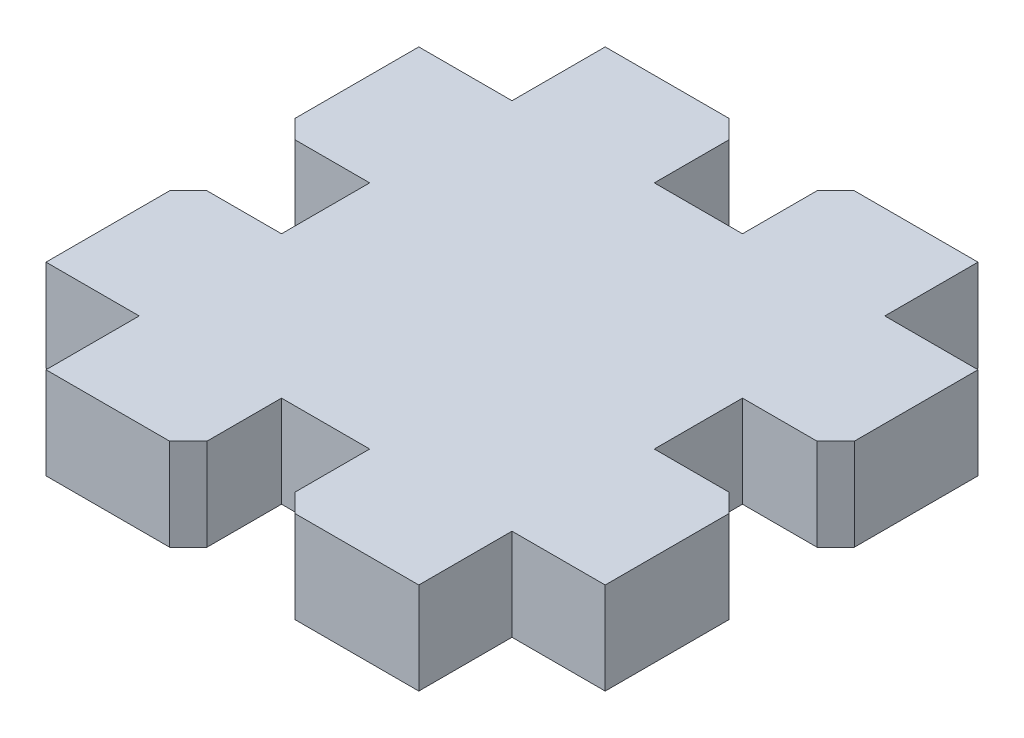
SolidWorks part; units mm, degrees
ref_plane "Front Plane" through (0, 0, 0) normal (0, 0, 1) x (1, 0, 0)
ref_plane "Top Plane" through (0, 0, 0) normal (0, 1, 0) x (1, 0, 0)
ref_plane "Right Plane" through (0, 0, 0) normal (1, 0, 0) x (0, 0, -1)
sketch "Sketch1" plane through (0, 0, 0) normal (0, 1, 0) x (1, 0, 0)
  line L0 (-3.0036, -11.2646) -> (-3.0036, -4.9146)
  line L1 (0, 0) -> (0, 21.9209) construction
  line L2 (-11.8657, 7.7854) -> (8.446, 7.7854) construction
  line L3 (0, 15.5709) -> (0, -6.35) construction
  line L4 (3.0036, 26.8354) -> (3.0036, 20.4854)
  line L5 (-3.0036, 20.4854) -> (3.0036, 20.4854)
  line L7 (-3.0036, 26.8354) -> (-3.0036, 20.4854)
  line L8 (12.7, 4.7819) -> (12.7, 10.789)
  line L9 (12.7, 10.789) -> (19.05, 10.789)
  line L11 (12.7, 4.7819) -> (19.05, 4.7819)
  line L12 (-12.7, 4.7819) -> (-19.05, 4.7819)
  line L14 (-12.7, 10.789) -> (-19.05, 10.789)
  line L16 (-12.7, 4.7819) -> (-12.7, 10.789)
  line L17 (-3.0036, -4.9146) -> (3.0036, -4.9146)
  line L18 (3.0036, -11.2646) -> (3.0036, -4.9146)
  line L19 (-12.7, 26.8354) -> (-3.0036, 26.8354)
  line L20 (-12.7, 26.8354) -> (-12.7, 20.4854)
  line L21 (-12.7, 20.4854) -> (-19.05, 20.4854)
  line L22 (-19.05, 20.4854) -> (-19.05, 10.789)
  line L23 (12.7, 26.8354) -> (3.0036, 26.8354)
  line L24 (12.7, 26.8354) -> (12.7, 20.4854)
  line L25 (12.7, 20.4854) -> (19.05, 20.4854)
  line L26 (19.05, 20.4854) -> (19.05, 10.789)
  line L27 (19.05, -4.9146) -> (19.05, 4.7819)
  line L28 (12.7, -4.9146) -> (19.05, -4.9146)
  line L29 (12.7, -11.2646) -> (12.7, -4.9146)
  line L30 (12.7, -11.2646) -> (3.0036, -11.2646)
  line L31 (-19.05, -4.9146) -> (-19.05, 4.7819)
  line L32 (-12.7, -4.9146) -> (-19.05, -4.9146)
  line L33 (-12.7, -11.2646) -> (-12.7, -4.9146)
  line L34 (-12.7, -11.2646) -> (-3.0036, -11.2646)
  point P3 (0, -4.9146)
  point P13 (0, 20.4854)
  point P22 (12.7, 7.7854)
  dimension "D1" = 12.7
  dimension "D3" = 9.6965
  dimension "2xslotdepth" = 12.7
  dimension "press_fit_slot" = 6.0071
extrude "Boss-Extrude1" add sketch "Sketch1" along normal blind 6.2611
chamfer "Chamfer1" distance 1.27 angle 45 8 edges at (3.0036, 3.1305, -26.8354) (-3.0036, 3.1305, -26.8354) (19.05, 3.1305, -10.789) (19.05, 3.1305, -4.7819) (3.0036, 3.1305, 11.2646) (-3.0036, 3.1305, 11.2646) (-19.05, 3.1305, -4.7819) (-19.05, 3.1305, -10.789)
equation "\"slot_width\"=0.2465"
equation "\"slot_depth\"= 0.25    "
equation "\"half_slot_width\"= \"slot_width\" /2"
equation "\"2xslotdepth\"= \"slot_depth\"*2"
equation "\"press_fit_slot\"= \"slot_width\"-0.01"
